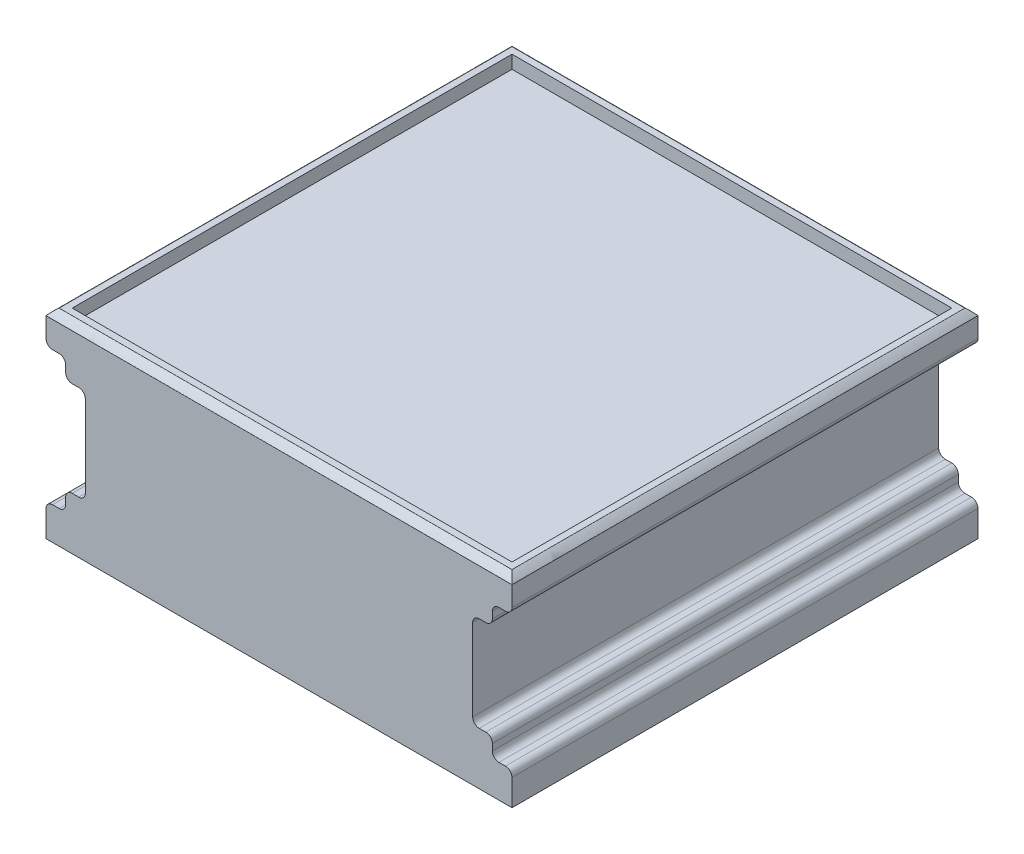
SolidWorks part; units mm, degrees
ref_plane "Front Plane" through (0, 0, 0) normal (0, 0, 1) x (1, 0, 0)
ref_plane "Top Plane" through (0, 0, 0) normal (0, 1, 0) x (1, 0, 0)
ref_plane "Right Plane" through (0, 0, 0) normal (1, 0, 0) x (0, 0, -1)
sketch "Sketch1" plane through (0, 0, 0) normal (0, 1, 0) x (1, 0, 0)
  line L1 (0, 0) -> (35.56, 0)
  line L2 (0, 0) -> (0, 35.56)
  line L3 (0, 35.56) -> (35.56, 35.56)
  line L4 (35.56, 0) -> (35.56, 35.56)
  dimension "D1" = 35.56
extrude "Boss-Extrude1" add sketch "Sketch1" along normal blind 15.24
sketch "Sketch2" plane through (0, 15.24, 0) normal (0, 1, 0) x (1, 0, 0)
  line L0 (17.78, 0) -> (17.78, 35.56) construction
  line L1 (0, 0) -> (35.56, 0) construction
  line L2 (35.56, 35.56) -> (0, 35.56) construction
  line L4 (1, 1) -> (34.56, 1)
  line L5 (1, 1) -> (1, 34.56)
  line L6 (1, 34.56) -> (34.56, 34.56)
  line L7 (34.56, 1) -> (34.56, 34.56)
  line L8 (1, 1) -> (34.56, 34.56) construction
  line L9 (1, 34.56) -> (34.56, 1) construction
  point P6 (17.78, 17.78)
  dimension "D1" = 1
extrude "Cut-Extrude1" cut sketch "Sketch2" against normal blind 1
sketch "Sketch3" plane through (0, 0, 0) normal (0, 0, 1) x (1, 0, 0)
  line L0 (0, 15.24) -> (0, 0) construction
  line L1 (0, 4) -> (3, 4)
  line L2 (0, 4) -> (0, 11.24)
  line L3 (0, 11.24) -> (3, 11.24)
  line L4 (3, 4) -> (3, 11.24)
  line L5 (3, 4) -> (3, 0) construction
  line L6 (0, 0) -> (35.56, 0) construction
  line L7 (3, 11.24) -> (3, 15.24) construction
  line L8 (0, 15.24) -> (35.56, 15.24) construction
  line L9 (17.78, 15.24) -> (17.78, 0) construction
  line L10 (32.56, 11.24) -> (32.56, 15.24) construction
  line L11 (32.56, 4) -> (32.56, 0) construction
  line L12 (32.56, 4) -> (32.56, 11.24)
  line L13 (35.56, 11.24) -> (32.56, 11.24)
  line L14 (35.56, 4) -> (35.56, 11.24)
  line L15 (35.56, 4) -> (32.56, 4)
  dimension "D1" = 4
  dimension "D2" = 3
extrude "Cut-Extrude2" cut sketch "Sketch3" against normal through all
sketch "Sketch4" plane through (0, 0, -35.56) normal (0, 0, -1) x (-1, 0, 0)
  line L1 (-35.56, 11.24) -> (-34.06, 11.24)
  line L2 (-35.56, 11.24) -> (-35.56, 12.74)
  line L3 (-35.56, 12.74) -> (-34.06, 12.74)
  line L4 (-34.06, 11.24) -> (-34.06, 12.74)
  line L5 (-35.56, 4) -> (-34.06, 4)
  line L6 (-35.56, 4) -> (-35.56, 2.5)
  line L7 (-35.56, 2.5) -> (-34.06, 2.5)
  line L8 (-34.06, 4) -> (-34.06, 2.5)
  line L9 (0, 4) -> (-1.5, 4)
  line L10 (0, 4) -> (0, 2.5)
  line L11 (0, 2.5) -> (-1.5, 2.5)
  line L12 (-1.5, 4) -> (-1.5, 2.5)
  line L13 (0, 11.24) -> (-1.5, 11.24)
  line L14 (0, 11.24) -> (0, 12.74)
  line L15 (0, 12.74) -> (-1.5, 12.74)
  line L16 (-1.5, 11.24) -> (-1.5, 12.74)
  dimension "D1" = 1.5
extrude "Cut-Extrude3" cut sketch "Sketch4" against normal through all
sketch "Sketch5" plane through (0, 0, -35.56) normal (0, 0, -1) x (-1, 0, 0)
  line L0 (-34.56, 14.49) -> (-34.56, 13.49)
  line L1 (-34.56, 13.49) -> (-33.06, 13.49)
  line L2 (-33.06, 13.49) -> (-33.06, 11.99)
  line L3 (-33.06, 11.99) -> (-31.56, 11.99)
  line L4 (-31.56, 11.99) -> (-31.56, 3.25)
  line L5 (-31.56, 3.25) -> (-33.06, 3.25)
  line L6 (-33.06, 3.25) -> (-33.06, 1.75)
  line L7 (-33.06, 1.75) -> (-34.56, 1.75)
  line L8 (-34.56, 1.75) -> (-34.56, 0.75)
  line L9 (-34.56, 0.75) -> (-1, 0.75)
  line L10 (-34.56, 14.49) -> (-1, 14.49)
  line L11 (-17.78, 15.24) -> (-17.78, 0) construction
  line L12 (-35.56, 15.24) -> (0, 15.24) construction
  line L13 (-35.56, 0) -> (0, 0) construction
  line L14 (-31.56, 7.62) -> (-4, 7.62) construction
  line L15 (-34.06, 12.74) -> (-35.56, 12.74) construction
  line L16 (-34.06, 11.24) -> (-32.56, 11.24) construction
  line L17 (-34.06, 11.24) -> (-34.06, 12.74) construction
  line L18 (-35.56, 15.24) -> (-35.56, 12.74) construction
  line L19 (-1, 1.75) -> (-1, 0.75)
  line L20 (-2.5, 1.75) -> (-1, 1.75)
  line L21 (-2.5, 3.25) -> (-2.5, 1.75)
  line L22 (-4, 3.25) -> (-2.5, 3.25)
  line L23 (-4, 11.99) -> (-4, 3.25)
  line L24 (-2.5, 11.99) -> (-4, 11.99)
  line L25 (-2.5, 13.49) -> (-2.5, 11.99)
  line L26 (-1, 13.49) -> (-2.5, 13.49)
  line L27 (-1, 14.49) -> (-1, 13.49)
  point P25 (-34.81, 12.74)
  point P27 (-32.934, 1.75)
  point P29 (-17.78, 7.62)
  point P30 (-17.78, 14.49)
  point P31 (-17.78, 0.75)
  dimension "D1" = 0.75
  dimension "D2" = 0.75
  dimension "D3" = 0.75
  dimension "D4" = 1
  dimension "D5" = 1
  dimension "D6" = 1
extrude "Cut-Extrude4" cut sketch "Sketch5" against normal blind 0.75
sketch "Sketch6" plane through (0, 0, -34.81) normal (0, 0, -1) x (-1, 0, 0)
  line L0 (-17.78, 0.75) -> (-17.78, 14.49) construction
  line L1 (-34.56, 0.75) -> (-1, 0.75) construction
  line L2 (-1, 14.49) -> (-34.56, 14.49) construction
  line L3 (-2.5, 13.49) -> (-1, 13.49) construction
  line L4 (-27.56, 1.75) -> (-8, 1.75)
  line L5 (-27.56, 1.75) -> (-27.56, 13.49)
  line L6 (-27.56, 13.49) -> (-8, 13.49)
  line L7 (-8, 1.75) -> (-8, 13.49)
  line L8 (-27.56, 1.75) -> (-8, 13.49) construction
  line L9 (-27.56, 13.49) -> (-8, 1.75) construction
  line L10 (-4, 3.25) -> (-4, 11.99) construction
  point P6 (-17.78, 7.62)
  point P11 (-17.78, 7.62)
  point P12 (-7.6168, 13.3195)
  dimension "D1" = 4
extrude "Boss-Extrude2" add sketch "Sketch6" along normal up to surface (0.75 mm away) up to face at (17.78, 7.62, -35.56)
fillet "Fillet1" radius 0.5 36 edges at (4, 11.99, -35.185) (1, 14.49, -35.185) (1, 13.49, -35.185) (2.5, 13.49, -35.185) (2.5, 11.99, -35.185) (1, 0.75, -35.185) (4, 3.25, -35.185) (2.5, 3.25, -35.185) (2.5, 1.75, -35.185) (1, 1.75, -35.185) (34.56, 0.75, -35.185) (34.56, 14.49, -35.185) (34.56, 13.49, -35.185) (33.06, 13.49, -35.185) (33.06, 11.99, -35.185) (31.56, 11.99, -35.185) (31.56, 3.25, -35.185) (33.06, 1.75, -35.185) (34.56, 1.75, -35.185) (33.06, 3.25, -35.185) (0, 2.5, -17.78) (1.5, 2.5, -17.78) (1.5, 4, -17.78) (3, 4, -17.78) (0, 12.74, -17.78) (1.5, 12.74, -17.78) (1.5, 11.24, -17.78) (3, 11.24, -17.78) (35.56, 12.74, -17.78) (34.06, 12.74, -17.78) (34.06, 11.24, -17.78) (32.56, 11.24, -17.78) (35.56, 2.5, -17.78) (34.06, 4, -17.78) (32.56, 4, -17.78) (34.06, 2.5, -17.78)
fillet "Fillet2" radius 0.5 4 edges at (17.78, 15.24, 0) (0, 15.24, -17.78) (17.78, 15.24, -35.56) (35.56, 15.24, -17.78) conic rho 0.05
